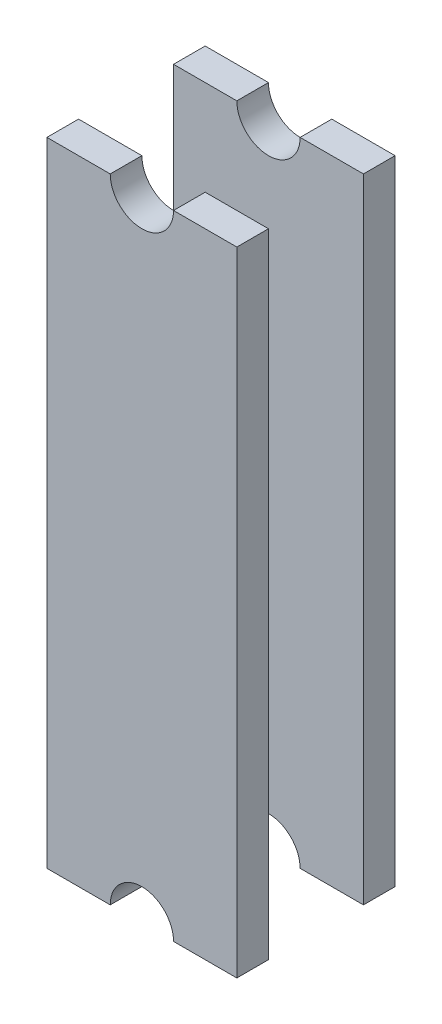
SolidWorks part; units mm, degrees
ref_plane "前视基准面" through (0, 0, 0) normal (0, 0, 1) x (1, 0, 0)
ref_plane "上视基准面" through (0, 0, 0) normal (0, 1, 0) x (1, 0, 0)
ref_plane "右视基准面" through (0, 0, 0) normal (1, 0, 0) x (0, 0, -1)
other "Configuration Table"
sketch "Sketch1" plane through (0, 0, 0) normal (0, 0, 1) x (1, 0, 0)
  line L1 (-30, 0) -> (30, 0)
  line L2 (-30, 0) -> (-30, 200)
  line L3 (-30, 200) -> (30, 200)
  line L4 (30, 0) -> (30, 200)
  line L5 (-30, 0) -> (30, 200) construction
  line L6 (-30, 200) -> (30, 0) construction
  point P0 (0, 100)
extrude "Boss-Extrude1" add sketch "Sketch1" along normal blind 10
ref_plane "Plane1" through (0, 0, 40) normal (0, 0, 1) x (1, 0, 0)
sketch "Sketch2" plane through (0, 0, 40) normal (0, 0, 1) x (1, 0, 0)
  line L1 (-30, 0) -> (30, 0)
  line L2 (-30, 0) -> (-30, 200)
  line L3 (-30, 200) -> (30, 200)
  line L4 (30, 0) -> (30, 200)
  line L5 (-30, 0) -> (30, 200) construction
  line L6 (-30, 200) -> (30, 0) construction
  point P0 (0, 100)
extrude "Boss-Extrude2" add sketch "Sketch2" along normal blind 10
sketch "Sketch3" plane through (0, 0, 0) normal (0, 0, 1) x (1, 0, 0)
  line L0 (30, 200) -> (-30, 200) construction
  circle A0 centre (0, 0) radius 10
  circle A1 centre (0, 200) radius 10
extrude "Cut-Extrude1" cut sketch "Sketch3" along normal blind 100
sketch3d "3DSketch1"
  line L0 (0, 0, -100) -> (0, 0, 100) construction
ref_axis "Axis_Bottom" through (0, 0, -100) along (0, 0, 1)
sketch3d "3DSketch2"
  line L0 (0, 200, -100) -> (0, 200, 100) construction
ref_axis "Axis_Top" through (0, 200, -100) along (0, 0, 1)
ref_plane "Mate_Mid" through (0, 0, 25) normal (0, 0, 1) x (1, 0, 0)
